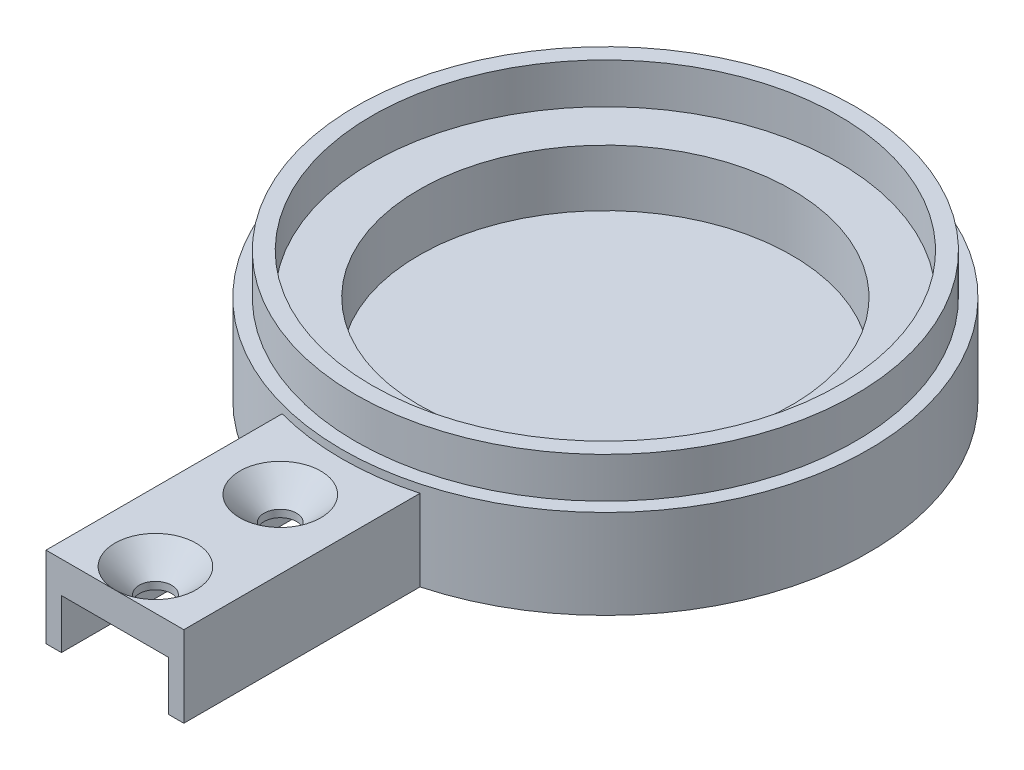
SolidWorks part; units mm, degrees
ref_plane "Plan de face" through (0, 0, 0) normal (0, 0, 1) x (1, 0, 0)
ref_plane "Plan de dessus" through (0, 0, 0) normal (0, 1, 0) x (1, 0, 0)
ref_plane "Plan de droite" through (0, 0, 0) normal (1, 0, 0) x (0, 0, -1)
sketch "Esquisse1" plane through (0, 0, 0) normal (0, 1, 0) x (1, 0, 0)
  circle A0 centre (0, 0) radius 32.5
  dimension "D1" = 65
extrude "Boss.-Extru.1" add sketch "Esquisse1" along normal blind 4
sketch "Esquisse2" plane through (0, 4, 0) normal (0, 1, 0) x (1, 0, 0)
  circle A0 centre (0, 0) radius 23
  circle A1 centre (0, 0) radius 32.5
  circle A2 centre (0, 0) radius 32.5 construction
  dimension "D1" = 46
extrude "Boss.-Extru.2" add sketch "Esquisse2" along normal blind 7
sketch "Esquisse4" plane through (0, 11, 0) normal (0, 1, 0) x (1, 0, 0)
  circle A0 centre (0, 0) radius 28.8
  circle A1 centre (0, 0) radius 30.8
  dimension "D1" = 57.6
  dimension "D2" = 61.6
extrude "Boss.-Extru.4" add sketch "Esquisse4" along normal blind 5
ref_plane "Plan1" through (0, 0, 32.5) normal (0, 0, 1) x (1, 0, 0)
sketch "Esquisse5" plane through (0, 0, 32.5) normal (0, 0, 1) x (1, 0, 0)
  line L0 (-32.5, 0) -> (32.5, 0) construction
  line L1 (8.5, 10) -> (-8.5, 10)
  line L2 (8.5, 10) -> (8.5, 0)
  line L3 (8.5, 0) -> (6.6, 0)
  line L4 (-8.5, 10) -> (-8.5, 0)
  line L5 (0, 10) -> (0, 0) construction
  line L6 (-6.6, 0) -> (-8.5, 0)
  line L8 (-6.6, 0) -> (-6.6, 6.1)
  line L9 (-6.6, 6.1) -> (6.6, 6.1)
  line L10 (6.6, 0) -> (6.6, 6.1)
  line L11 (0, 6.1) -> (0, 2.7086) construction
  dimension "D1" = 17
  dimension "D2" = 10
  dimension "D3" = 13.2
  dimension "D4" = 3.9
extrude "Boss.-Extru.5" add sketch "Esquisse5" along normal blind 28 and the other way blind 2
sketch "Esquisse6" plane through (0, 10, 0) normal (0, 1, 0) x (1, 0, 0)
  line L0 (0, -60.5) -> (0, -32.0251) construction
  line L1 (8.5, -60.5) -> (-8.5, -60.5) construction
  line L2 (-6.6, -60.5) -> (6.6, -60.5) construction
  circle A0 centre (0, -55.5) radius 2
  circle A1 centre (0, -40.1) radius 2
  point P9 (0, 0)
  point P10 (0, 0)
  dimension "D1" = 4
  dimension "D2" = 4
  dimension "D3" = 15.4
  dimension "D4" = 5
extrude "Enlèv. mat.-Extru.1" cut sketch "Esquisse6" against normal blind 5
chamfer "Chanfrein1" distance 3 angle 45 2 edges at (-2, 10, 40.1) (-2, 10, 55.5)
equation "\"D2@Esquisse4\"=\"D1@Esquisse4\"+4"
equation "\"D4@Esquisse5\"=(\"D1@Esquisse5\"-\"D3@Esquisse5\")/2+2"
equation "\"D2@Esquisse6\"=\"D1@Esquisse6\""
equation "\"D3@Esquisse6\"=18.6-3.2"
